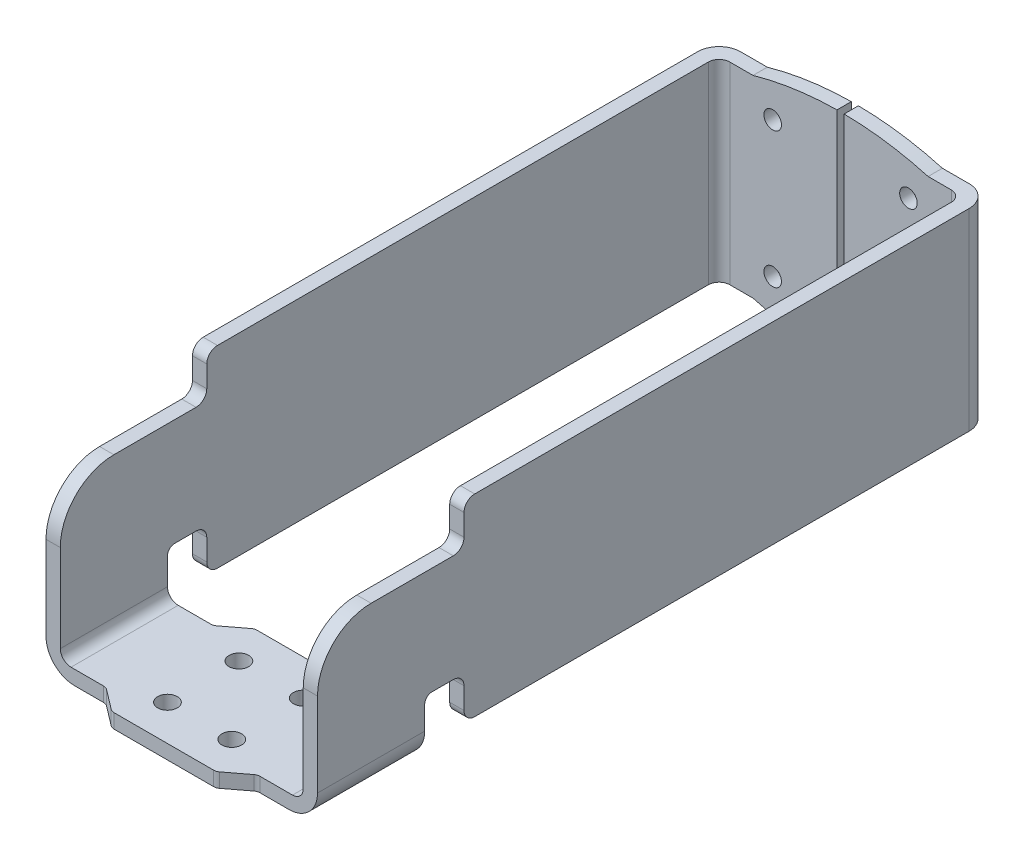
SolidWorks part; units mm, degrees
material "1.0037 (S235JR)"
ref_plane "Front Plane" through (0, 0, 0) normal (0, 0, 1) x (1, 0, 0)
ref_plane "Top Plane" through (0, 0, 0) normal (0, 1, 0) x (1, 0, 0)
ref_plane "Right Plane" through (0, 0, 0) normal (1, 0, 0) x (0, 0, -1)
ref_plane "Plane1" through (0, 0, -193.4) normal (0, 0, 1) x (1, 0, 0)
sketch "Sketch1" plane through (0, 0, -193.4) normal (0, 0, 1) x (1, 0, 0)
  line L0 (-38, 58.5) -> (-38, 4.5)
  line L1 (-38, 4.5) -> (-24.5039, 4.5)
  line L2 (24.5039, 4.5) -> (38, 4.5)
  line L3 (38, 4.5) -> (38, 58.5)
  line L4 (38, 58.5) -> (24.5039, 58.5)
  line L5 (-24.5039, 58.5) -> (-38, 58.5)
  arc A0 (-24.5039, 4.5) -> (24.5039, 4.5) centre (0, 91.1) ccw
  arc A1 (24.5039, 58.5) -> (-24.5039, 58.5) centre (0, -28.1) ccw
extrude "Boss-Extrude1" add sketch "Sketch1" along normal blind 193.4
sketch "Sketch2" plane through (0, 0, 0) normal (1, 0, 0) x (0, 0, -1)
  line L0 (0, -5) -> (189.4, -5)
  line L1 (189.4, -5) -> (189.4, 4.5)
  line L2 (189.4, 4.5) -> (49, 4.5)
  line L3 (46, 7.5) -> (46, 13.5)
  line L4 (43, 16.5) -> (37, 16.5)
  line L5 (35, 14.5) -> (35, 0)
  line L6 (35, 0) -> (5, 0)
  line L7 (5, 0) -> (5, 31.5)
  line L8 (20, 46.5) -> (43, 46.5)
  line L9 (46, 49.5) -> (46, 55.5)
  line L10 (49, 58.5) -> (189.4, 58.5)
  line L11 (189.4, 58.5) -> (189.4, 63.5)
  line L12 (189.4, 63.5) -> (0, 63.5)
  line L13 (0, 63.5) -> (0, -5)
  arc A0 (49, 4.5) -> (46, 7.5) centre (49, 7.5) cw
  arc A1 (46, 13.5) -> (43, 16.5) centre (43, 13.5) ccw
  arc A2 (37, 16.5) -> (35, 14.5) centre (37, 14.5) ccw
  arc A3 (5, 31.5) -> (20, 46.5) centre (20, 31.5) cw
  arc A4 (43, 46.5) -> (46, 49.5) centre (43, 49.5) ccw
  arc A5 (46, 55.5) -> (49, 58.5) centre (49, 55.5) cw
extrude "Cut-Extrude1" cut sketch "Sketch2" along normal blind 38 and the other way blind 38
sketch "Sketch3" plane through (0, 0, 0) normal (0, 1, 0) x (1, 0, 0)
  line L0 (-38, 5) -> (-21.865, 5)
  line L1 (-20.6546, 4.5922) -> (-15.1504, 0.4078)
  line L2 (-13.94, 0) -> (13.94, 0)
  line L3 (15.1504, 0.4078) -> (20.6546, 4.5922)
  line L4 (21.865, 5) -> (38, 5)
  line L5 (38, 5) -> (38, 35)
  line L6 (38, 35) -> (21.865, 35)
  line L7 (20.6546, 35.4078) -> (15.1504, 39.5922)
  line L8 (13.94, 40) -> (-13.94, 40)
  line L9 (-15.1504, 39.5922) -> (-20.6546, 35.4078)
  line L10 (-21.865, 35) -> (-38, 35)
  line L11 (-38, 35) -> (-38, 5)
  arc A0 (-21.865, 5) -> (-20.6546, 4.5922) centre (-21.865, 3) cw
  arc A1 (-15.1504, 0.4078) -> (-13.94, 0) centre (-13.94, 2) ccw
  arc A2 (13.94, 0) -> (15.1504, 0.4078) centre (13.94, 2) ccw
  arc A3 (20.6546, 4.5922) -> (21.865, 5) centre (21.865, 3) cw
  arc A4 (21.865, 35) -> (20.6546, 35.4078) centre (21.865, 37) cw
  arc A5 (15.1504, 39.5922) -> (13.94, 40) centre (13.94, 38) ccw
  arc A6 (-13.94, 40) -> (-15.1504, 39.5922) centre (-13.94, 38) ccw
  arc A7 (-20.6546, 35.4078) -> (-21.865, 35) centre (-21.865, 37) cw
extrude "Boss-Extrude2" add sketch "Sketch3" along normal blind 4.5
sketch "Sketch4" plane through (0, 0, 0) normal (0, 0, 1) x (1, 0, 0)
  line L0 (-38, -5) -> (38, -5)
  line L1 (38, -5) -> (38, 8)
  line L2 (30, 0) -> (-30, 0)
  line L3 (-38, 8) -> (-38, -5)
  arc A0 (38, 8) -> (30, 0) centre (30, 8) cw
  arc A1 (-30, 0) -> (-38, 8) centre (-30, 8) cw
extrude "Cut-Extrude2" cut sketch "Sketch4" against normal blind 40
sketch "Sketch5" plane through (0, 0, 0) normal (0, 0, 1) x (1, 0, 0)
  line L0 (-31, 4) -> (31, 4)
  line L1 (34, 7) -> (34, 62)
  line L2 (34, 62) -> (-34, 62)
  line L3 (-34, 62) -> (-34, 7)
  arc A0 (-34, 7) -> (-31, 4) centre (-31, 7) ccw
  arc A1 (31, 4) -> (34, 7) centre (31, 7) ccw
extrude "Cut-Extrude3" cut sketch "Sketch5" against normal blind 42
sketch "Sketch6" plane through (0, 0, 0) normal (0, 1, 0) x (1, 0, 0)
  line L0 (-34, 186.4) -> (-34, 41)
  line L1 (-34, 41) -> (34, 41)
  line L2 (34, 41) -> (34, 186.4)
  line L3 (31, 189.4) -> (-31, 189.4)
  arc A0 (34, 186.4) -> (31, 189.4) centre (31, 186.4) ccw
  arc A1 (-31, 189.4) -> (-34, 186.4) centre (-31, 186.4) ccw
extrude "Cut-Extrude4" cut sketch "Sketch6" along normal blind 81.5
sketch "Sketch7" plane through (0, 0, 0) normal (0, 1, 0) x (1, 0, 0)
  line L0 (-32, 193.4) -> (32, 193.4)
  line L1 (38, 187.4) -> (38, 198.4)
  line L2 (38, 198.4) -> (-38, 198.4)
  line L3 (-38, 198.4) -> (-38, 187.4)
  arc A0 (-38, 187.4) -> (-32, 193.4) centre (-32, 187.4) cw
  arc A1 (32, 193.4) -> (38, 187.4) centre (32, 187.4) cw
extrude "Cut-Extrude5" cut sketch "Sketch7" along normal blind 81.5
sketch "Sketch8" plane through (0, 0, -193.4) normal (0, 0, 1) x (1, 0, 0)
  line L0 (-1, 0) -> (1, 0)
  line L1 (1, 0) -> (1, 108)
  line L2 (1, 108) -> (-1, 108)
  line L3 (-1, 108) -> (-1, 0)
extrude "Cut-Extrude6" cut sketch "Sketch8" along normal blind 4
ref_plane "Plane2" through (9, 0, 0) normal (1, 0, 0) x (0, 0, -1)
sketch "Sketch9" plane through (9, 0, 0) normal (1, 0, 0) x (0, 0, -1)
  line L0 (10, 4) -> (12.75, 4)
  line L1 (12.75, 4) -> (12.75, 0)
  line L2 (12.75, 0) -> (10, 0)
  line L3 (10, 0) -> (10, 4)
  line L4 (10, 0) -> (10, 4) construction
revolve "Cut-Revolve1" cut sketch "Sketch9" angle 360 about L4 reverse direction yes
sketch "Sketch10" plane through (0, 0, 0) normal (0, 1, 0) x (1, 0, 0)
  line L0 (9, 10) -> (9, 30)
  line L1 (9, 10) -> (-9, 10)
pattern_linear "LPattern1" count 2 spacing 20 along (0, 0, -1) count 2 spacing 18 along (-1, 0, 0) of "Cut-Revolve1"
ref_plane "Plane3" through (19, 0, 0) normal (1, 0, 0) x (0, 0, -1)
sketch "Sketch11" plane through (19, 0, 0) normal (1, 0, 0) x (0, 0, -1)
  line L0 (189.4, 12.5) -> (189.4, 14.9585)
  line L1 (189.4, 14.9585) -> (192.8585, 14.9585)
  line L2 (192.8585, 14.9585) -> (193.4, 15.5)
  line L3 (193.4, 15.5) -> (193.4, 12.5)
  line L4 (193.4, 12.5) -> (189.4, 12.5)
  line L5 (193.4, 12.5) -> (189.4, 12.5) construction
revolve "Cut-Revolve2" cut sketch "Sketch11" angle 360 about L5 reverse direction yes
cosmetic thread "Cosmetic Thread1" parameters "D1"=4, "D2"=6
sketch "Sketch12" plane through (0, 0, -193.4) normal (0, 0, 1) x (1, 0, 0)
  line L0 (19, 12.5) -> (19, 50.5)
  line L1 (19, 12.5) -> (-19, 12.5)
pattern_linear "LPattern2" count 2 spacing 38 along (0, 1, 0) count 2 spacing 38 along (-1, 0, 0) of "Cut-Revolve2"
cosmetic thread "Cosmetic Thread2" parameters "D1"=4, "D2"=6
cosmetic thread "Cosmetic Thread3" parameters "D1"=4, "D2"=6
cosmetic thread "Cosmetic Thread4" parameters "D1"=4, "D2"=6
ref_plane "Plane4" through (0, 5.8, 0) normal (0, 1, 0) x (1, 0, 0)
ref_plane "ANBAU XY" through (0, 0, -193.4) normal (0, 0, 1) x (1, 0, 0)
ref_plane "ANBAU XZ" through (0, 0, 0) normal (0, -1, 0) x (-1, 0, 0)
ref_plane "ANBAU YZ" through (0, 0, 0) normal (1, 0, 0) x (0, 0, -1)
ref_axis "ANBAU X" through (-80.9, 0, -193.4) along (1, 0, 0)
ref_axis "ANBAU Y" through (0, -50, -193.4) along (0, 1, 0)
ref_axis "ANBAU Z" through (0, 0, 80.9) along (0, 0, -1)
sketch3d "ANBAU"
  point P0 (0, 0, -193.4)
ref_plane "IP1 1 XY" through (0, 0, 0) normal (0, 1, 0) x (1, 0, 0)
ref_plane "IP1 1 XZ" through (0, 0, -10) normal (0, 0, 1) x (1, 0, 0)
ref_plane "IP1 1 YZ" through (9, 0, 0) normal (1, 0, 0) x (0, 0, -1)
ref_axis "IP1 1 X" through (-80.9, 0, -10) along (1, 0, 0)
ref_axis "IP1 1 Y" through (9, 0, 50) along (0, 0, -1)
ref_axis "IP1 1 Z" through (9, 50, -10) along (0, -1, 0)
sketch3d "IP1 1"
  point P0 (9, 0, -10)
ref_plane "IP1 2 XY" through (0, 0, 0) normal (0, 1, 0) x (1, 0, 0)
ref_plane "IP1 2 XZ" through (0, 0, -10) normal (0, 0, 1) x (1, 0, 0)
ref_plane "IP1 2 YZ" through (-9, 0, 0) normal (1, 0, 0) x (0, 0, -1)
ref_axis "IP1 2 X" through (-80.9, 0, -10) along (1, 0, 0)
ref_axis "IP1 2 Y" through (-9, 0, 50) along (0, 0, -1)
ref_axis "IP1 2 Z" through (-9, 50, -10) along (0, -1, 0)
sketch3d "IP1 2"
  point P0 (-9, 0, -10)
ref_plane "IP1 3 XY" through (0, 0, 0) normal (0, 1, 0) x (1, 0, 0)
ref_plane "IP1 3 XZ" through (0, 0, -30) normal (0, 0, 1) x (1, 0, 0)
ref_plane "IP1 3 YZ" through (9, 0, 0) normal (1, 0, 0) x (0, 0, -1)
ref_axis "IP1 3 X" through (-80.9, 0, -30) along (1, 0, 0)
ref_axis "IP1 3 Y" through (9, 0, 50) along (0, 0, -1)
ref_axis "IP1 3 Z" through (9, 50, -30) along (0, -1, 0)
sketch3d "IP1 3"
  point P0 (9, 0, -30)
ref_plane "IP1 4 XY" through (0, 0, 0) normal (0, 1, 0) x (1, 0, 0)
ref_plane "IP1 4 XZ" through (0, 0, -30) normal (0, 0, 1) x (1, 0, 0)
ref_plane "IP1 4 YZ" through (-9, 0, 0) normal (1, 0, 0) x (0, 0, -1)
ref_axis "IP1 4 X" through (-80.9, 0, -30) along (1, 0, 0)
ref_axis "IP1 4 Y" through (-9, 0, 50) along (0, 0, -1)
ref_axis "IP1 4 Z" through (-9, 50, -30) along (0, -1, 0)
sketch3d "IP1 4"
  point P0 (-9, 0, -30)
ref_plane "IP2 1 XY" through (0, 0, -193.4) normal (0, 0, 1) x (1, 0, 0)
ref_plane "IP2 1 XZ" through (0, 12.5, 0) normal (0, -1, 0) x (-1, 0, 0)
ref_plane "IP2 1 YZ" through (19, 0, 0) normal (1, 0, 0) x (0, 0, -1)
ref_axis "IP2 1 X" through (-80.9, 12.5, -193.4) along (1, 0, 0)
ref_axis "IP2 1 Y" through (19, -50, -193.4) along (0, 1, 0)
ref_axis "IP2 1 Z" through (19, 12.5, 80.9) along (0, 0, -1)
sketch3d "IP2 1"
  point P0 (19, 12.5, -193.4)
ref_plane "IP2 2 XY" through (0, 0, -193.4) normal (0, 0, 1) x (1, 0, 0)
ref_plane "IP2 2 XZ" through (0, 12.5, 0) normal (0, -1, 0) x (-1, 0, 0)
ref_plane "IP2 2 YZ" through (-19, 0, 0) normal (1, 0, 0) x (0, 0, -1)
ref_axis "IP2 2 X" through (-80.9, 12.5, -193.4) along (1, 0, 0)
ref_axis "IP2 2 Y" through (-19, -50, -193.4) along (0, 1, 0)
ref_axis "IP2 2 Z" through (-19, 12.5, 80.9) along (0, 0, -1)
sketch3d "IP2 2"
  point P0 (-19, 12.5, -193.4)
ref_plane "IP2 3 XY" through (0, 0, -193.4) normal (0, 0, 1) x (1, 0, 0)
ref_plane "IP2 3 XZ" through (0, 50.5, 0) normal (0, -1, 0) x (-1, 0, 0)
ref_plane "IP2 3 YZ" through (19, 0, 0) normal (1, 0, 0) x (0, 0, -1)
ref_axis "IP2 3 X" through (-80.9, 50.5, -193.4) along (1, 0, 0)
ref_axis "IP2 3 Y" through (19, -50, -193.4) along (0, 1, 0)
ref_axis "IP2 3 Z" through (19, 50.5, 80.9) along (0, 0, -1)
sketch3d "IP2 3"
  point P0 (19, 50.5, -193.4)
ref_plane "IP2 4 XY" through (0, 0, -193.4) normal (0, 0, 1) x (1, 0, 0)
ref_plane "IP2 4 XZ" through (0, 50.5, 0) normal (0, -1, 0) x (-1, 0, 0)
ref_plane "IP2 4 YZ" through (-19, 0, 0) normal (1, 0, 0) x (0, 0, -1)
ref_axis "IP2 4 X" through (-80.9, 50.5, -193.4) along (1, 0, 0)
ref_axis "IP2 4 Y" through (-19, -50, -193.4) along (0, 1, 0)
ref_axis "IP2 4 Z" through (-19, 50.5, 80.9) along (0, 0, -1)
sketch3d "IP2 4"
  point P0 (-19, 50.5, -193.4)
ref_plane "TO_NUT 1 XY" through (0, 5.8, 0) normal (0, -1, 0) x (-1, 0, 0)
ref_plane "TO_NUT 1 XZ" through (0, 0, -10) normal (0, 0, -1) x (-1, 0, 0)
ref_plane "TO_NUT 1 YZ" through (9, 0, 0) normal (1, 0, 0) x (0, 0, -1)
ref_axis "TO_NUT 1 X" through (-80.9, 5.8, -10) along (1, 0, 0)
ref_axis "TO_NUT 1 Y" through (9, 5.8, -50) along (0, 0, 1)
ref_axis "TO_NUT 1 Z" through (9, -50, -10) along (0, 1, 0)
sketch3d "TO_NUT 1"
  point P0 (9, 5.8, -10)
ref_plane "TO_NUT 2 XY" through (0, 5.8, 0) normal (0, -1, 0) x (-1, 0, 0)
ref_plane "TO_NUT 2 XZ" through (0, 0, -10) normal (0, 0, -1) x (-1, 0, 0)
ref_plane "TO_NUT 2 YZ" through (-9, 0, 0) normal (1, 0, 0) x (0, 0, -1)
ref_axis "TO_NUT 2 X" through (-80.9, 5.8, -10) along (1, 0, 0)
ref_axis "TO_NUT 2 Y" through (-9, 5.8, -50) along (0, 0, 1)
ref_axis "TO_NUT 2 Z" through (-9, -50, -10) along (0, 1, 0)
sketch3d "TO_NUT 2"
  point P0 (-9, 5.8, -10)
other "Freeze***"
